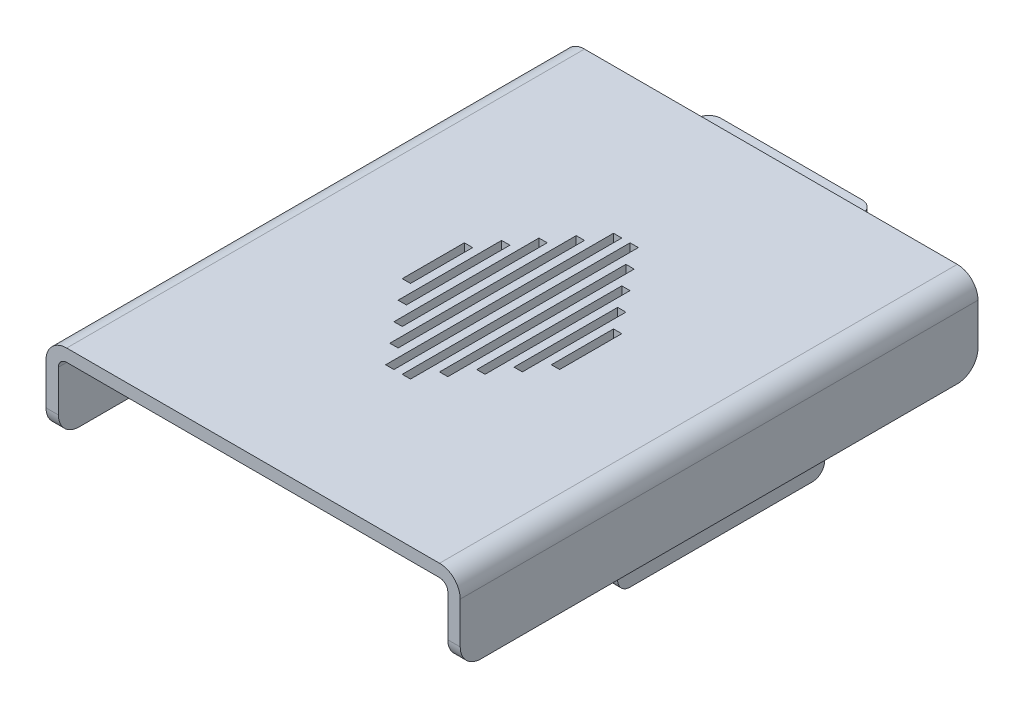
SolidWorks part; units mm, degrees
material "ABS"
ref_plane "Front Plane" through (0, 0, 0) normal (0, 0, 1) x (1, 0, 0)
ref_plane "Top Plane" through (0, 0, 0) normal (0, 1, 0) x (1, 0, 0)
ref_plane "Right Plane" through (0, 0, 0) normal (1, 0, 0) x (0, 0, -1)
sketch "Sketch1" plane through (0, 0, 0) normal (0, 0, 1) x (1, 0, 0)
  line L0 (-62.3906, 20.6479) -> (-62.3906, 26.5485) construction
  line L1 (-62.3906, 20.6479) -> (-62.3906, -14.3521) construction
  line L2 (-15.3906, 5.6479) -> (-15.3906, 20.6479)
  line L4 (-17.3906, 22.6479) -> (-107.3906, 22.6479)
  line L5 (-109.3906, 20.6479) -> (-109.3906, 5.6479)
  line L6 (-109.3906, 5.6479) -> (-112.3906, 5.6479)
  line L7 (-15.3906, 5.6479) -> (-12.3906, 5.6479)
  line L16 (-17.3906, 25.6479) -> (-107.3906, 25.6479)
  line L17 (-112.3906, 20.6479) -> (-112.3906, 5.6479)
  line L23 (-12.3906, 5.6479) -> (-12.3906, 20.6479)
  arc A0 (-107.3906, 25.6479) -> (-112.3906, 20.6479) centre (-107.3906, 20.6479) ccw
  arc A1 (-17.3906, 25.6479) -> (-12.3906, 20.6479) centre (-17.3906, 20.6479) cw
  arc A2 (-17.3906, 22.6479) -> (-15.3906, 20.6479) centre (-17.3906, 20.6479) cw
  arc A3 (-107.3906, 22.6479) -> (-109.3906, 20.6479) centre (-107.3906, 20.6479) ccw
  dimension "D4" = 20
  dimension "D5" = 100
  dimension "D1" = 5
  dimension "D2" = 3
  dimension "D3" = 20
extrude "Boss-Extrude1" add sketch "Sketch1" along normal blind 125
fillet "Fillet1" radius 5 4 edges at (-13.8906, 5.6479, 125) (-13.8906, 5.6479, 0) (-110.8906, 5.6479, 0) (-110.8906, 5.6479, 125)
sketch "Sketch2" plane through (0, 5.6479, 0) normal (0, -1, 0) x (1, 0, 0)
  line L1 (-107.3906, 35) -> (-110.3906, 35)
  line L2 (-107.3906, 35) -> (-107.3906, 85)
  line L3 (-107.3906, 85) -> (-110.3906, 85)
  line L4 (-110.3906, 35) -> (-110.3906, 85)
  line L6 (-82.3535, 85) -> (-109.3906, 85) construction
  line L7 (-109.3906, 120) -> (-109.3906, 5) construction
  line L9 (-12.3906, 35) -> (-12.3906, 85) construction
  line L10 (-15.3906, 85) -> (-12.3906, 85) construction
  line L11 (-15.3906, 35) -> (-15.3906, 85) construction
  line L12 (-15.3906, 35) -> (-12.3906, 35) construction
extrude "Boss-Extrude2" add sketch "Sketch2" against normal blind 18 and the other way blind 5
sketch "Sketch12" plane through (0, 5.6479, 0) normal (0, -1, 0) x (1, 0, 0)
  line L0 (-62.3906, 125) -> (-62.3906, 0) construction
  line L1 (-107.3906, 125) -> (-17.3906, 125) construction
  line L2 (-107.3906, 0) -> (-17.3906, 0) construction
  line L3 (-14.3906, 35) -> (-17.3906, 35)
  line L4 (-107.3906, 35) -> (-107.3906, 85)
  line L5 (-107.3906, 85) -> (-110.3906, 85)
  line L6 (-110.3906, 85) -> (-110.3906, 35)
  line L7 (-110.3906, 35) -> (-107.3906, 35)
  line L8 (-107.3906, 35) -> (-107.3906, 85) construction
  line L9 (-107.3906, 85) -> (-110.3906, 85) construction
  line L10 (-110.3906, 85) -> (-110.3906, 35) construction
  line L11 (-110.3906, 35) -> (-107.3906, 35) construction
  line L12 (-14.3906, 85) -> (-14.3906, 35)
  line L13 (-17.3906, 85) -> (-14.3906, 85)
  line L14 (-17.3906, 35) -> (-17.3906, 85)
  dimension "D1" = 0
extrude "Boss-Extrude5" add sketch "Sketch12" against normal blind 18 and the other way blind 5
sketch "Sketch3" plane through (0, 22.6479, 0) normal (0, -1, 0) x (1, 0, 0)
  line L0 (-62.3906, 0) -> (-62.3906, 120) construction
  line L1 (-42.3906, 10) -> (-82.3906, 10)
  line L2 (-42.3906, 10) -> (-42.3906, -5)
  line L3 (-42.3906, -5) -> (-82.3906, -5)
  line L4 (-82.3906, 10) -> (-82.3906, -5)
  line L5 (-62.3906, 125) -> (-62.3906, 127.9312) construction
  line L6 (-12.3906, 0) -> (-12.3906, 5) construction
  line L7 (-107.3906, 125) -> (-17.3906, 125) construction
  dimension "D1" = 20
  dimension "D2" = 40
  dimension "D3" = 15
  dimension "D4" = 50
extrude "Boss-Extrude3" add sketch "Sketch3" along normal blind 3
chamfer "Chamfer1" distance 4 angle 45 1 edges at (-62.3906, 22.6479, 10)
fillet "Fillet3" radius 4 2 edges at (-62.3906, 19.6479, 11) (-62.3906, 22.6479, 14)
fillet "Fillet4" radius 3 2 edges at (-82.3906, 21.1479, -5) (-42.3906, 21.1479, -5)
sketch "Sketch13" plane through (0, 25.6479, 0) normal (0, 1, 0) x (1, 0, 0)
  line L0 (-62.3906, 0) -> (-62.3906, -125) construction
  line L1 (-43.3906, -55) -> (-43.3906, -70)
  line L2 (-17.3906, -125) -> (-107.3906, -125) construction
  line L3 (-17.3906, 0) -> (-107.3906, 0) construction
  line L4 (-63.3906, -35) -> (-65.3906, -35)
  line L5 (-63.3906, -35) -> (-63.3906, -90)
  line L6 (-63.3906, -90) -> (-65.3906, -90)
  line L7 (-65.3906, -35) -> (-65.3906, -90)
  line L8 (-62.3906, -62.5) -> (-51.3906, -62.5) construction
  line L10 (-67.3906, -40) -> (-69.3906, -40)
  line L11 (-67.3906, -40) -> (-67.3906, -85)
  line L12 (-67.3906, -85) -> (-69.3906, -85)
  line L13 (-69.3906, -40) -> (-69.3906, -85)
  line L14 (-71.3906, -45) -> (-73.3906, -45)
  line L15 (-71.3906, -45) -> (-71.3906, -80)
  line L16 (-71.3906, -80) -> (-73.3906, -80)
  line L17 (-73.3906, -45) -> (-73.3906, -80)
  line L21 (-55.3906, -40) -> (-55.3906, -85)
  line L22 (-57.3906, -85) -> (-55.3906, -85)
  line L23 (-57.3906, -40) -> (-57.3906, -85)
  line L24 (-57.3906, -40) -> (-55.3906, -40)
  line L25 (-59.3906, -35) -> (-59.3906, -90)
  line L26 (-61.3906, -90) -> (-59.3906, -90)
  line L27 (-61.3906, -35) -> (-61.3906, -90)
  line L28 (-61.3906, -35) -> (-59.3906, -35)
  line L29 (-75.3906, -50) -> (-77.3906, -50)
  line L30 (-75.3906, -50) -> (-75.3906, -75)
  line L31 (-75.3906, -75) -> (-77.3906, -75)
  line L32 (-77.3906, -50) -> (-77.3906, -75)
  line L33 (-79.3906, -55) -> (-81.3906, -55)
  line L34 (-79.3906, -55) -> (-79.3906, -70)
  line L35 (-79.3906, -70) -> (-81.3906, -70)
  line L36 (-81.3906, -55) -> (-81.3906, -70)
  line L37 (-45.3906, -70) -> (-43.3906, -70)
  line L38 (-45.3906, -55) -> (-45.3906, -70)
  line L39 (-45.3906, -55) -> (-43.3906, -55)
  line L40 (-47.3906, -50) -> (-47.3906, -75)
  line L41 (-49.3906, -75) -> (-47.3906, -75)
  line L42 (-49.3906, -50) -> (-49.3906, -75)
  line L43 (-49.3906, -50) -> (-47.3906, -50)
  line L44 (-51.3906, -45) -> (-51.3906, -80)
  line L45 (-53.3906, -80) -> (-51.3906, -80)
  line L46 (-53.3906, -45) -> (-53.3906, -80)
  line L47 (-53.3906, -45) -> (-51.3906, -45)
extrude "Cut-Extrude1" cut sketch "Sketch13" against normal up to surface (3 mm away) up to face at (-62.3906, 22.6479, 43.4428)
sketch "Sketch14" plane through (0, 22.6479, 0) normal (0, 1, 0) x (1, 0, 0)
  circle A1 centre (-62.3906, -116) radius 7.5
  circle A3 centre (-62.3906, -116) radius 7.5
  dimension "D1" = 0
extrude "Cut-Extrude2" cut sketch "Sketch14" along normal blind 2
fillet "Fillet5" radius 3 4 edges at (-108.8906, 0.6479, 85) (-108.8906, 0.6479, 35) (-15.8906, 0.6479, 35) (-15.8906, 0.6479, 85)
fillet "Fillet6" radius 3 2 edges at (-17.3906, 22.6479, 60) (-107.3906, 22.6479, 60)
